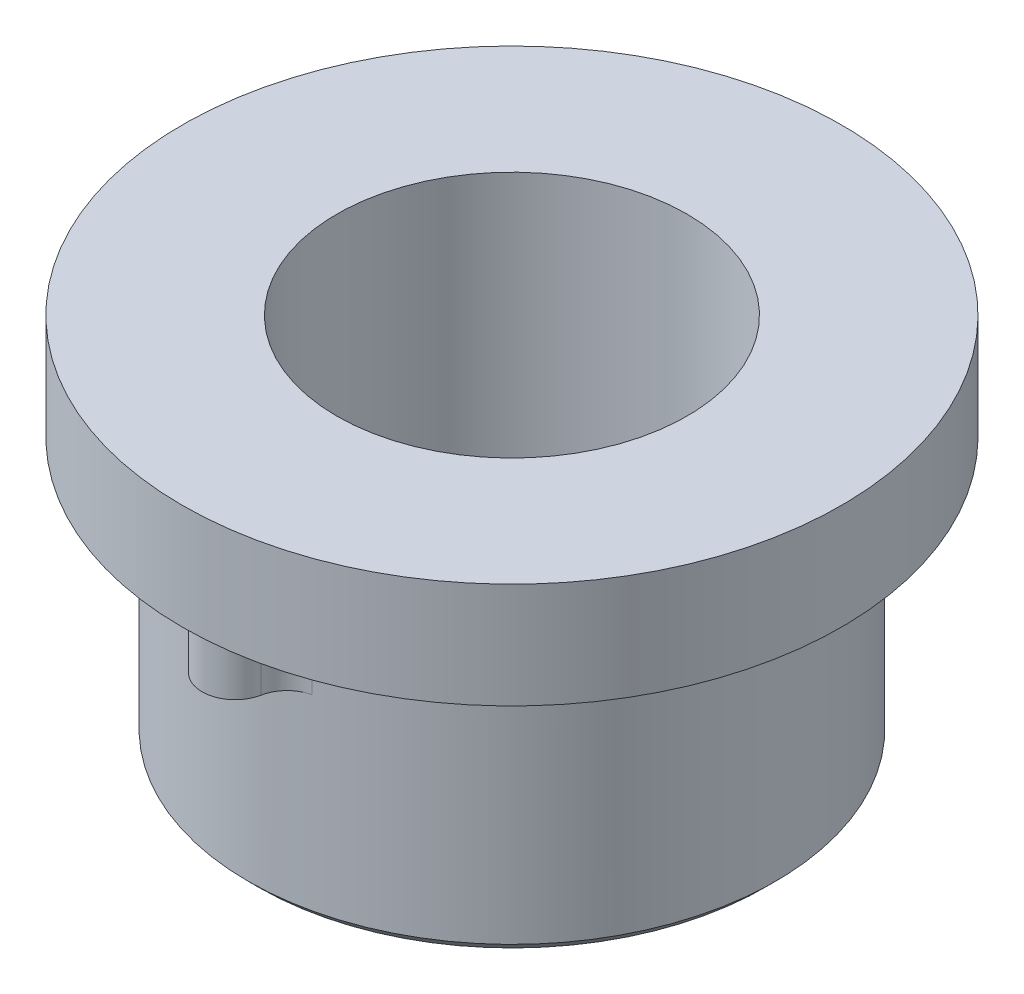
SolidWorks part; units mm, degrees
material "6061-T6 (SS)"
ref_plane "Front Plane" through (0, 0, 0) normal (0, 0, 1) x (1, 0, 0)
ref_plane "Top Plane" through (0, 0, 0) normal (0, 1, 0) x (1, 0, 0)
ref_plane "Right Plane" through (0, 0, 0) normal (1, 0, 0) x (0, 0, -1)
sketch "Sketch2" plane through (0, 0, 0) normal (0, 1, 0) x (1, 0, 0)
  circle A0 centre (0, 0) radius 6.35
  dimension "D1" = 12.7
extrude "Boss-Extrude1" add sketch "Sketch2" along normal blind 6.35
sketch "Sketch3" plane through (0, 6.35, 0) normal (0, 1, 0) x (1, 0, 0)
  circle A0 centre (0, 0) radius 7.9375
  dimension "D1" = 15.875
extrude "Boss-Extrude2" add sketch "Sketch3" along normal blind 2.54
sketch "Sketch8" plane through (0, 6.35, 0) normal (0, -1, 0) x (1, 0, 0)
  line L0 (0, -6.6675) -> (0, 6.6675) construction
  line L1 (-0.7937, -6.6675) -> (-0.7938, 6.6675)
  line L2 (0.7937, -6.6675) -> (0.7937, 6.6675)
  arc A0 (-0.7937, -6.6675) -> (0.7937, -6.6675) centre (0, -6.6675) ccw
  arc A1 (0.7937, 6.6675) -> (-0.7938, 6.6675) centre (0, 6.6675) ccw
  point P2 (0, 0)
  dimension "D1" = 1.5875
  dimension "D2" = 13.335
extrude "Boss-Extrude3" add sketch "Sketch8" along normal blind 1.5875
hole_wizard "3/8-24 Tapped Hole1" positions "Sketch6" profile "Sketch7" tap size "3/8-24" standard "Ansi Inch"
sketch "Sketch6" plane through (0, 8.89, 0) normal (0, 1, 0) x (-1, 0, 0)
  point P0 (0, 0)
sketch "Sketch7" plane through (0, 8.89, 0) normal (1, 0, 0) x (0, 0, 1)
  line L0 (0, 0) -> (0, 24.8855)
  line L1 (0, 24.8855) -> (4.2164, 22.352)
  line L2 (4.2164, 22.352) -> (4.2164, 0)
  line L5 (4.2164, 0) -> (0, 0)
  line L10 (0, 24.8855) -> (-4.2164, 22.352) construction
  line L11 (0, -6.35) -> (0, 107.95) construction
  dimension "Tap Drill Dia." = 8.4328
  dimension "Tap Drill Depth" = 22.352
  dimension "Drill Angle" = 118
chamfer "Chamfer1" distance 0.254 angle 45 1 edges at (0, 0, 6.35)
fillet "Fillet1" radius 0.7937 4 edges at (0.7937, 5.5562, -6.3002) (-0.7938, 5.5562, -6.3002) (-0.7938, 5.5562, 6.3002) (0.7937, 5.5562, 6.3002)
